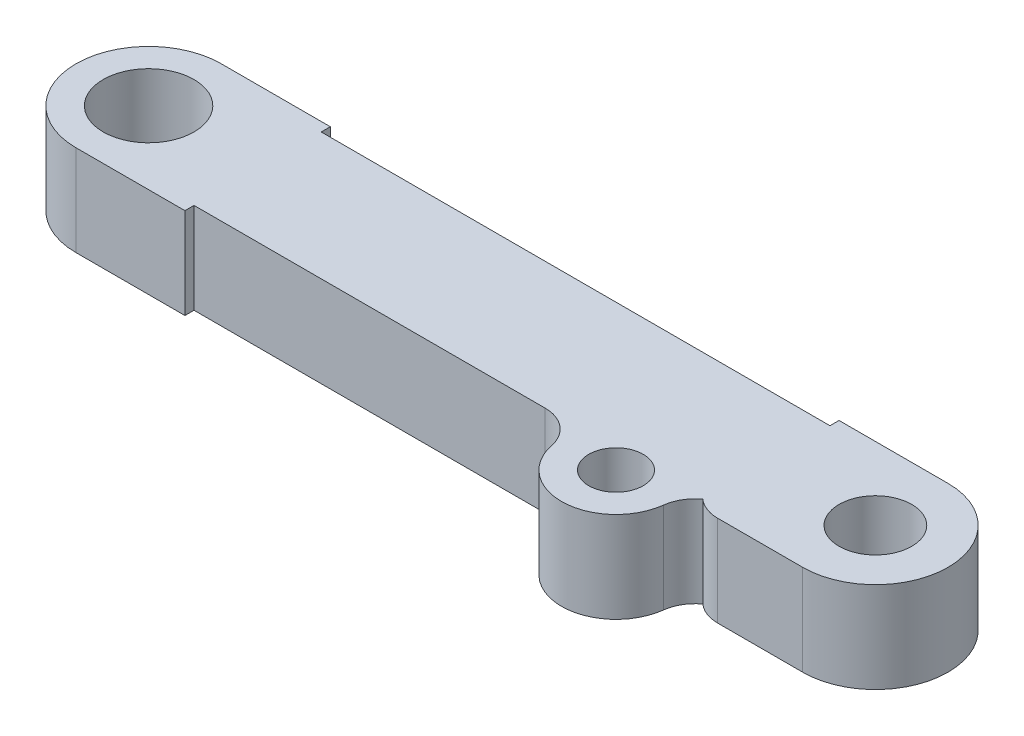
SolidWorks part; units mm, degrees
ref_plane "Front" through (0, 0, 0) normal (0, 0, 1) x (1, 0, 0)
ref_plane "Top" through (0, 0, 0) normal (0, 1, 0) x (1, 0, 0)
ref_plane "Right" through (0, 0, 0) normal (1, 0, 0) x (0, 0, -1)
sketch "Sketch1" plane through (0, 0, 0) normal (0, 1, 0) x (1, 0, 0)
  line L0 (0, 80) -> (120, 80)
  line L1 (0, -80) -> (120, -80)
  line L2 (120, 80) -> (120, 70)
  line L3 (680, 80) -> (800, 80)
  line L4 (680, 80) -> (680, 70)
  line L5 (680, -80) -> (800, -80)
  line L6 (120, -70) -> (120, -80)
  line L7 (120, 70) -> (680, 70)
  line L8 (120, -70) -> (547.9114, -70)
  line L9 (680, -70) -> (680, -80)
  line L10 (661.0485, -70) -> (680, -70)
  arc A0 (0, 80) -> (0, -80) centre (0, 0) ccw
  arc A1 (800, -80) -> (800, 80) centre (800, 0) ccw
  circle A2 centre (604.4799, -90) radius 30
  arc A3 (547.9114, -70) -> (661.0485, -70) centre (604.4799, -90) ccw
  circle A4 centre (0, 0) radius 50
  circle A5 centre (800, 0) radius 40
  dimension "D1" = 120
  dimension "D2" = 160
  dimension "D3" = 120
  dimension "D4" = 90
  dimension "D5" = 800
extrude "Boss-Extrude1" add sketch "Sketch1" along normal blind 100
fillet "Fillet1" radius 40 1 edges at (547.9114, 50, 70)
fillet "Fillet2" radius 40 1 edges at (661.0485, 50, 70)
fillet "Fillet3" radius 40 1 edges at (680, 50, 80)
